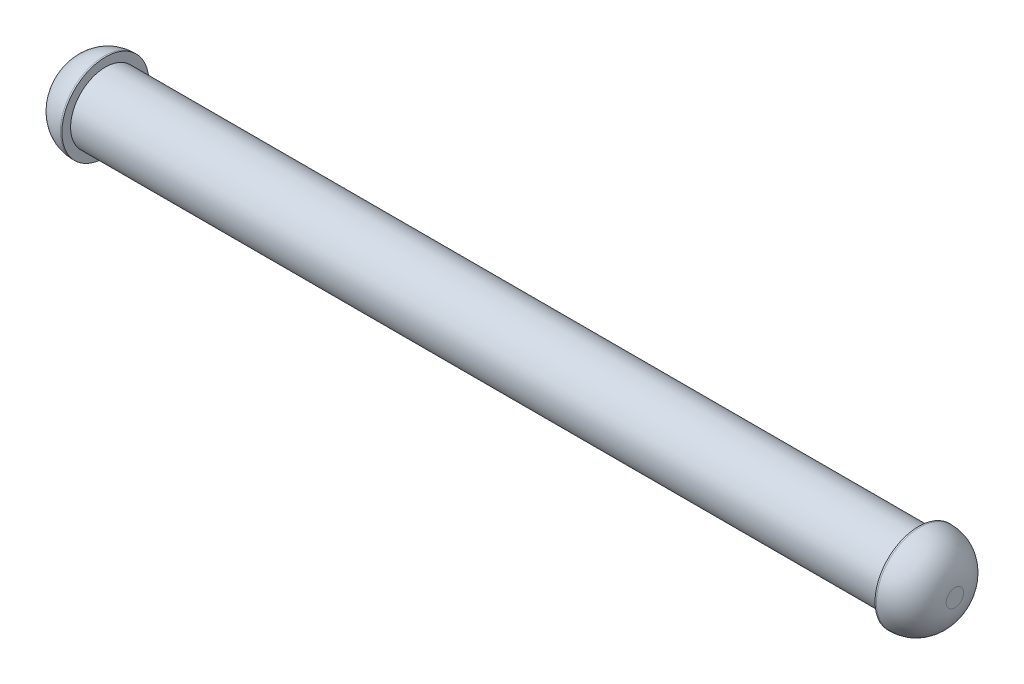
SolidWorks part; units mm, degrees
ref_plane "Front Plane" through (0, 0, 0) normal (0, 0, 1) x (1, 0, 0)
ref_plane "Top Plane" through (0, 0, 0) normal (0, 1, 0) x (1, 0, 0)
ref_plane "Right Plane" through (0, 0, 0) normal (1, 0, 0) x (0, 0, -1)
sketch "Sketch1" plane through (0, 0, 0) normal (0, 1, 0) x (1, 0, 0)
  line L0 (-76.25, 0) -> (76.25, 0) construction
  line L1 (0, 0) -> (0, 96.6088) construction
  line L2 (-76.25, 0) -> (-76.25, 7.5)
  line L3 (-76.25, 7.5) -> (-70, 7.5)
  line L4 (-70, 7.5) -> (-70, 6)
  line L5 (-70, 6) -> (70, 6)
  line L6 (-76.25, 0) -> (76.25, 0)
  line L7 (70, 7.5) -> (70, 6)
  line L8 (76.25, 7.5) -> (70, 7.5)
  line L9 (76.25, 0) -> (76.25, 7.5)
  point P10 (0, 6)
  dimension "D1" = 70
  dimension "D2" = 6.25
  dimension "D3" = 6
  dimension "D4" = 7.5
revolve "Revolve1" add sketch "Sketch1" angle 360 about L6
fillet "Fillet1" radius 6 2 edges at (-76.25, 0, 7.5) (76.25, 0, 7.5)
